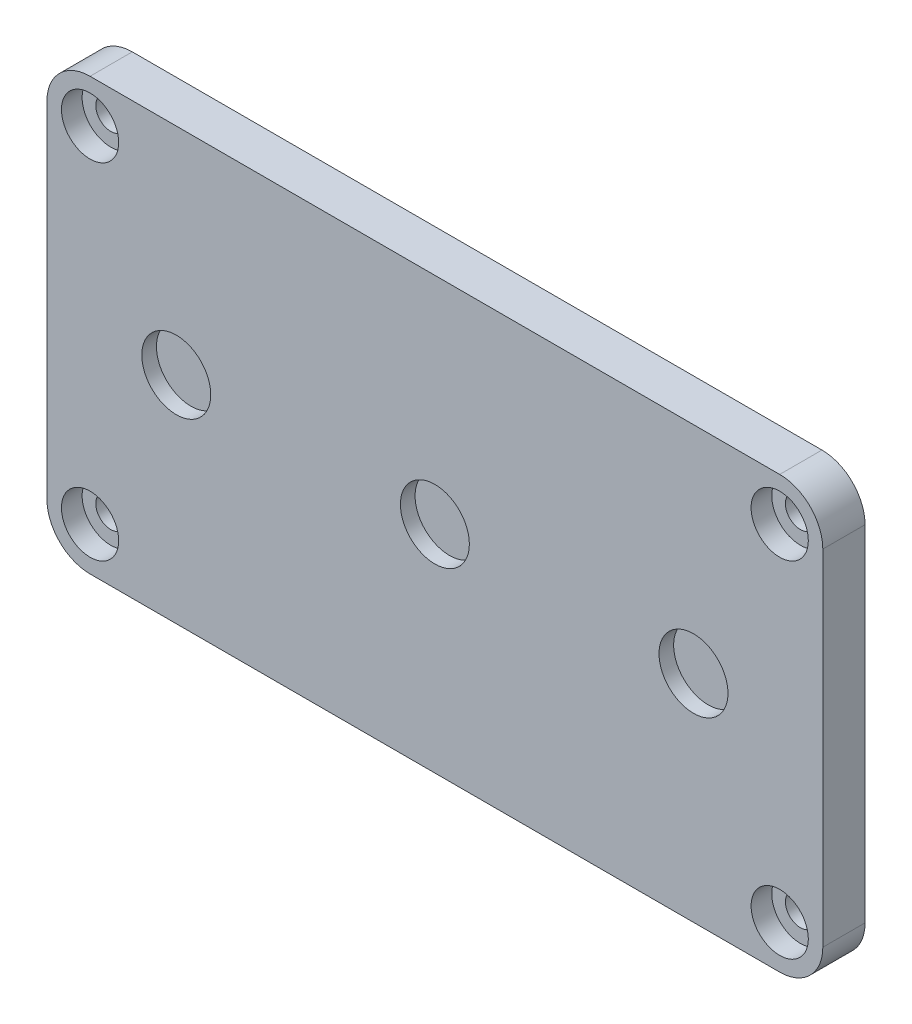
SolidWorks part; units mm, degrees
material "ABS"
ref_plane "Front Plane" through (0, 0, 0) normal (0, 0, 1) x (1, 0, 0)
ref_plane "Top Plane" through (0, 0, 0) normal (0, 1, 0) x (1, 0, 0)
ref_plane "Right Plane" through (0, 0, 0) normal (1, 0, 0) x (0, 0, -1)
sketch "Sketch1" plane through (0, 0, 0) normal (0, 0, 1) x (1, 0, 0)
  line L1 (-50.8, -31.75) -> (50.8, -31.75)
  line L2 (-57.15, -25.4) -> (-57.15, 25.4)
  line L3 (-50.8, 31.75) -> (50.8, 31.75)
  line L4 (57.15, -25.4) -> (57.15, 25.4)
  line L5 (-57.15, -31.75) -> (57.15, 31.75) construction
  line L6 (-57.15, 31.75) -> (57.15, -31.75) construction
  arc A0 (50.8, -31.75) -> (57.15, -25.4) centre (50.8, -25.4) ccw
  arc A1 (50.8, 31.75) -> (57.15, 25.4) centre (50.8, 25.4) cw
  arc A2 (-57.15, 25.4) -> (-50.8, 31.75) centre (-50.8, 25.4) cw
  arc A3 (-50.8, -31.75) -> (-57.15, -25.4) centre (-50.8, -25.4) cw
  circle A4 centre (-50.8, -25.4) radius 2.2098
  circle A5 centre (-50.8, 25.4) radius 2.2098
  circle A6 centre (50.8, 25.4) radius 2.2098
  circle A7 centre (50.8, -25.4) radius 2.2098
  point P0 (0, 0)
  dimension "D3" = 6.35
  dimension "D4" = 4.4196
  dimension "D1" = 114.3
  dimension "D2" = 63.5
extrude "Boss-Extrude1" add sketch "Sketch1" along normal blind 6.223
sketch "Sketch2" plane through (0, 0, 6.223) normal (0, 0, 1) x (1, 0, 0)
  circle A0 centre (-50.8, 25.4) radius 4.2164
  circle A1 centre (50.8, 25.4) radius 4.2164
  circle A2 centre (50.8, -25.4) radius 4.2164
  circle A3 centre (-50.8, -25.4) radius 4.2164
  dimension "D1" = 8.4328
extrude "Cut-Extrude1" cut sketch "Sketch2" against normal blind 3.048
sketch "Sketch3" plane through (0, 0, 6.223) normal (0, 0, 1) x (1, 0, 0)
  circle A0 centre (0, 0) radius 5.08
  circle A1 centre (38.1, 0) radius 5.08
  circle A2 centre (-38.1, 0) radius 5.08
  dimension "D3" = 10.16
  dimension "D1" = 38.1
  dimension "D2" = 38.1
extrude "Cut-Extrude2" cut sketch "Sketch3" against normal blind 2.159
equation "\"tolerance\"= 0.005"
equation "\"D1@Boss-Extrude1\"= .115 + .125 + \"tolerance\""
equation "\"D4@Sketch1\" = .164 + \"tolerance\" * 2"
equation "\"D1@Sketch2\"= .322 + \"tolerance\" * 2"
equation "\"D1@Cut-Extrude1\"= .115 + \"tolerance\""
equation "\"D3@Sketch3\"= .39 + \"tolerance\" * 2"
equation "\"D1@Cut-Extrude2\"= .08 + \"tolerance\""
